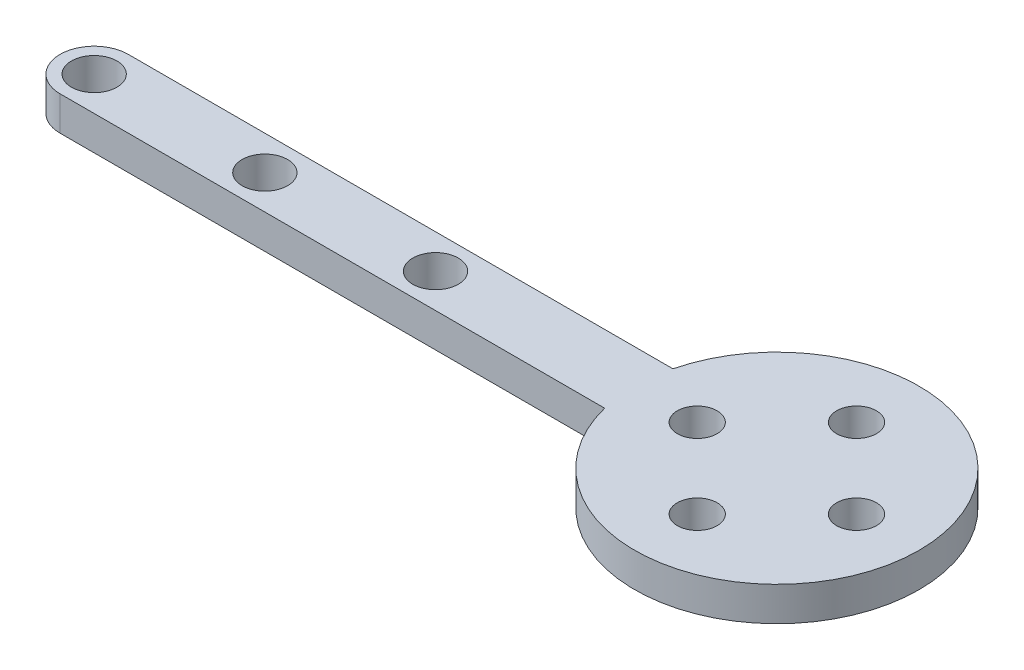
SolidWorks part; units mm, degrees
ref_plane "前视基准面" through (0, 0, 0) normal (0, 0, 1) x (1, 0, 0)
ref_plane "上视基准面" through (0, 0, 0) normal (0, 1, 0) x (1, 0, 0)
ref_plane "右视基准面" through (0, 0, 0) normal (1, 0, 0) x (0, 0, -1)
sketch "草图1" plane through (0, 0, 0) normal (0, 1, 0) x (1, 0, 0)
  line L0 (0, 0) -> (0, 7) construction
  line L1 (0, 0) -> (-60, 0) construction
  line L2 (-12.1347, -3) -> (-60, -3)
  line L3 (-12.1347, 3) -> (-60, 3)
  arc A0 (-12.1347, -3) -> (-12.1347, 3) centre (0, 0) ccw
  circle A1 centre (0, 7) radius 1.75
  circle A2 centre (7, 0) radius 1.75
  circle A3 centre (0, -7) radius 1.75
  circle A4 centre (-7, 0) radius 1.75
  arc A6 (-60, 3) -> (-60, -3) centre (-60, 0) ccw
  circle A7 centre (-60, 0) radius 2
  circle A8 centre (-30, 0) radius 2
  circle A9 centre (-45, 0) radius 2
  point P5 (-30, 0)
  point P14 (0, 0)
  point P20 (-12.1347, 3)
  point P21 (-12.1347, -3)
  dimension "D1" = 3.5
  dimension "D4" = 25
  dimension "D7" = 4
  dimension "D8" = 4
  dimension "D9" = 4
  dimension "D3" = 14
  dimension "D5" = 6
  dimension "D6" = 60
  dimension "D10" = 15
  dimension "D2" = 4
extrude "凸台-拉伸1" add sketch "草图1" along normal blind 3
